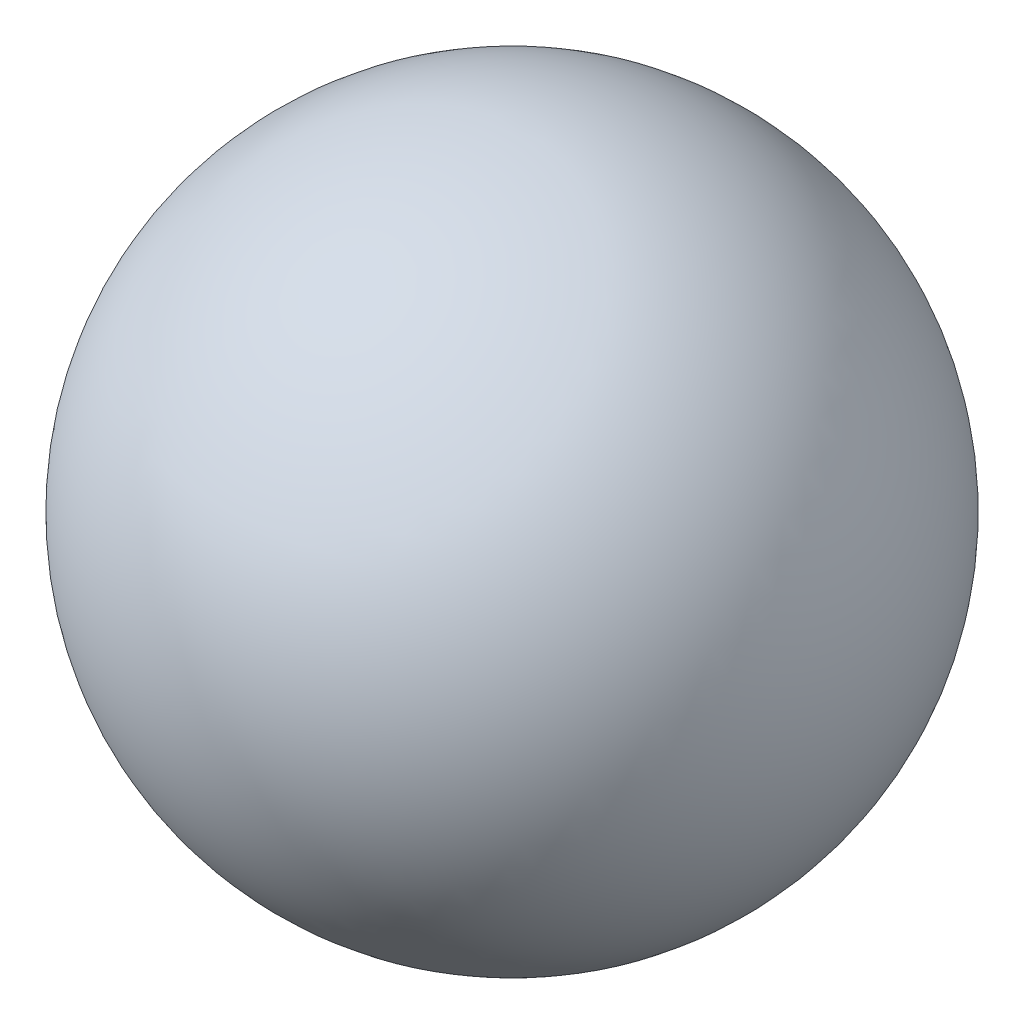
SolidWorks part; units mm, degrees
material "Plain Carbon Steel"
ref_plane "Front Plane" through (0, 0, 0) normal (0, 0, 1) x (1, 0, 0)
ref_plane "Top Plane" through (0, 0, 0) normal (0, 1, 0) x (1, 0, 0)
ref_plane "Right Plane" through (0, 0, 0) normal (1, 0, 0) x (0, 0, -1)
sketch "Sketch1" plane through (0, 0, 0) normal (0, 0, 1) x (1, 0, 0)
  line L0 (0, 4) -> (0, -4)
  arc A0 (0, 4) -> (0, -4) centre (0, 0) cw
  point P4 (0, 0)
  dimension "D1" = 8
revolve "Revolve1" add sketch "Sketch1" angle 360 about L0
ref_axis "Axis1" through (0, 4, 0) along (0, -1, 0)
ref_plane "Plane1" through (0, 4, 0) normal (0, 1, 0) x (1, 0, 0)
